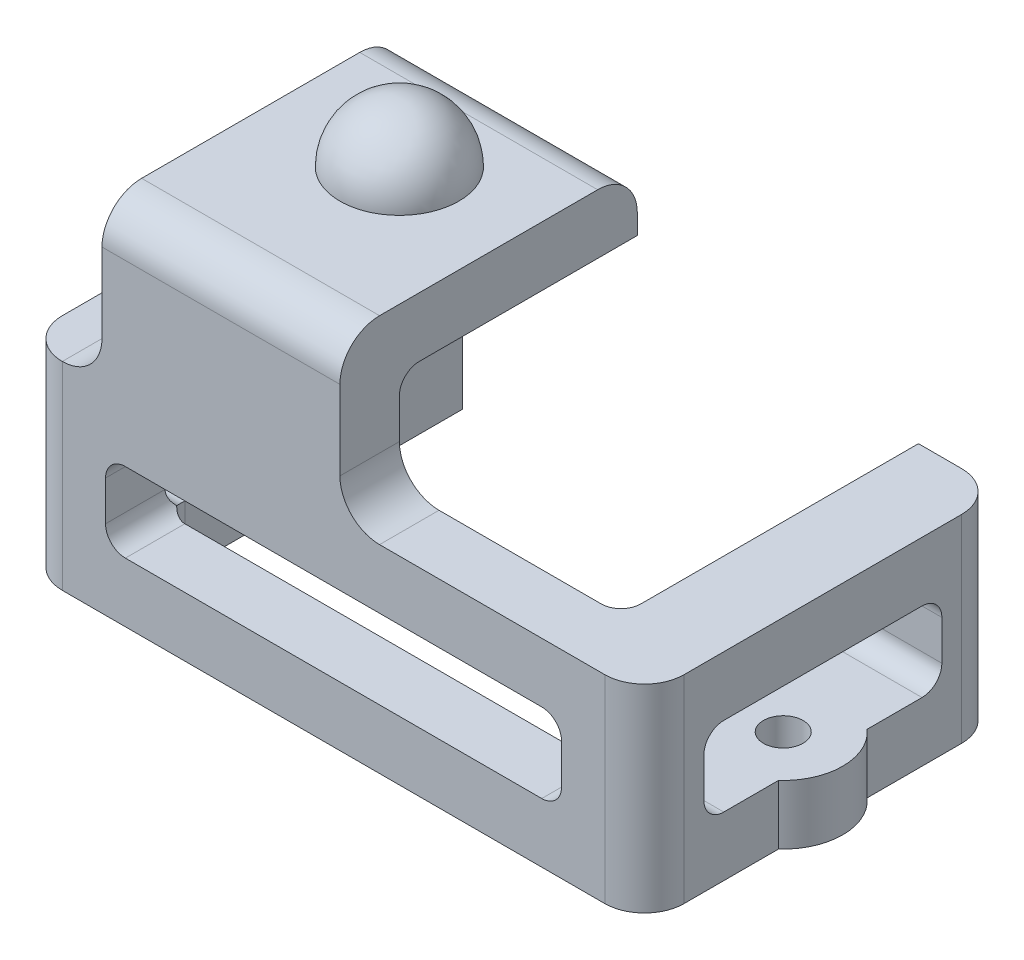
SolidWorks part; units mm, degrees
ref_plane "Plano frontal" through (0, 0, 0) normal (0, 0, 1) x (1, 0, 0)
ref_plane "Plano superior" through (0, 0, 0) normal (0, 1, 0) x (1, 0, 0)
ref_plane "Plano direito" through (0, 0, 0) normal (1, 0, 0) x (0, 0, -1)
sketch "Sketch1" plane through (0, 0, 0) normal (0, 1, 0) x (1, 0, 0)
  line L1 (-15.68, -9) -> (15.68, -9)
  line L2 (-15.68, -9) -> (-15.68, 9)
  line L3 (-15.68, 9) -> (15.68, 9)
  line L4 (15.68, -9) -> (15.68, 9)
  line L5 (-15.68, -9) -> (15.68, 9) construction
  line L6 (-15.68, 9) -> (15.68, -9) construction
  point P0 (0, 0)
  dimension "D1" = 31.36
  dimension "D2" = 18
extrude "Boss-Extrude1" add sketch "Sketch1" along normal mid plane 3
sketch "Sketch2" plane through (0, 1.5, 0) normal (0, 1, 0) x (1, 0, 0)
  line L0 (15.68, 9) -> (-15.68, 9) construction
  line L5 (-11.5, 9) -> (11.5, 9)
  line L6 (-11.5, 9) -> (-11.5, -6)
  line L7 (-11.5, -6) -> (11.5, -6)
  line L8 (11.5, 9) -> (11.5, -6)
  point P0 (0, 0)
  point P5 (0, 9)
  dimension "D1" = 23
  dimension "D2" = 6
extrude "Cut-Extrude1" cut sketch "Sketch2" against normal up to next
sketch "Sketch3" plane through (0, 1.5, 0) normal (0, 1, 0) x (1, 0, 0)
  line L1 (11.5, -6) -> (11.5, 9) construction
  line L2 (-11.5, 9) -> (-11.5, -6) construction
  circle A0 centre (13.68, 0) radius 1
  circle A1 centre (-13.68, 0) radius 1
  point P2 (0, 0)
  point P3 (25.9303, -1.6202)
  point P4 (0, 0)
  dimension "D3" = 2
  dimension "D4" = 2
  dimension "D1" = 2.18
  dimension "D2" = 2.18
extrude "Cut-Extrude2" cut sketch "Sketch3" against normal up to next
sketch "Sketch5" plane through (0, 1.5, 0) normal (0, 1, 0) x (1, 0, 0)
  line L0 (15.68, -9) -> (15.68, 9) construction
  line L1 (-11.5, 6) -> (-15.68, 6)
  line L2 (-11.5, 6) -> (-11.5, 9)
  line L3 (-11.5, 9) -> (-15.68, 9)
  line L4 (-15.68, 6) -> (-15.68, 9)
  line L5 (11.5, 6) -> (15.68, 6)
  line L6 (11.5, 6) -> (11.5, 9)
  line L7 (11.5, 9) -> (15.68, 9)
  line L8 (15.68, 6) -> (15.68, 9)
  line L9 (11.5, -9) -> (15.68, -9)
  line L10 (11.5, -9) -> (11.5, -6)
  line L11 (11.5, -6) -> (15.68, -6)
  line L12 (15.68, -9) -> (15.68, -6)
  line L14 (-15.68, -9) -> (-11.5, -9)
  line L15 (-15.68, -9) -> (-15.68, -6)
  line L16 (-15.68, -6) -> (-11.5, -6)
  line L17 (-11.5, -9) -> (-11.5, -6)
  line L20 (11.5, -6) -> (11.5, 9) construction
  line L21 (-11.5, 9) -> (-11.5, -6) construction
  point P24 (0, 0)
  point P26 (12.505, -6.4128)
  point P32 (15.5, -7.1503)
  dimension "D2" = 3
  dimension "D3" = 3
  dimension "D1" = 3
extrude "Boss-Extrude3" add sketch "Sketch5" along normal blind 4
sketch "Sketch6" plane through (0, 5.5, 0) normal (0, 1, 0) x (1, 0, 0)
  line L1 (-15.68, 9) -> (15.68, 9)
  line L2 (-15.68, 9) -> (-15.68, -9)
  line L3 (-15.68, -9) -> (15.68, -9)
  line L4 (15.68, 9) -> (15.68, -9)
extrude "Boss-Extrude4" add sketch "Sketch6" along normal blind 3
sketch "Sketch7" plane through (0, 5.5, 0) normal (0, -1, 0) x (1, 0, 0)
  line L1 (-11.5, 6) -> (11.5, 6)
  line L2 (-11.5, 6) -> (-11.5, -9)
  line L3 (-11.5, -9) -> (11.5, -9)
  line L4 (11.5, 6) -> (11.5, -9)
  line L6 (11.5, -9) -> (11.5, -6) construction
  line L7 (-11.5, -6) -> (-11.5, -9) construction
  line L8 (-11.5, 6) -> (-15.68, 6) construction
  line L9 (11.5, -9) -> (-11.5, -9) construction
  point P6 (0, 0)
  point P8 (0, 0)
  point P12 (0, 0)
extrude "Cut-Extrude3" cut sketch "Sketch7" against normal up to next
sketch "Sketch8" plane through (0, 0, 9) normal (0, 0, 1) x (1, 0, 0)
  line L0 (-15.68, 8.5) -> (15.68, 8.5) construction
  line L1 (-11.68, 8.5) -> (0.32, 8.5)
  line L2 (-11.68, 8.5) -> (-11.68, 13.5)
  line L3 (-11.68, 13.5) -> (0.32, 13.5)
  line L4 (0.32, 8.5) -> (0.32, 13.5)
  line L5 (-15.68, 8.5) -> (-15.68, -1.5) construction
  point P6 (-5.68, 13.5)
  dimension "D1" = 10
  dimension "D2" = 5
  dimension "D3" = 12
extrude "Boss-Extrude5" add sketch "Sketch8" against normal up to surface (3 mm away) up to face at (0, 7, 6)
sketch "Sketch9" plane through (0, 0, 6) normal (0, 0, -1) x (-1, 0, 0)
  line L0 (11.68, 8.5) -> (11.68, 13.5) construction
  line L1 (-0.32, 13.5) -> (11.68, 13.5)
  line L2 (-0.32, 13.5) -> (-0.32, 16.5)
  line L3 (-0.32, 16.5) -> (11.68, 16.5)
  line L4 (11.68, 13.5) -> (11.68, 16.5)
  dimension "D1" = 3
extrude "Boss-Extrude6" add sketch "Sketch9" along normal blind 12 and the other way up to surface (3 mm away) contours L4 L3 L2 L1 other way up to face at (-2.84, 7.25, 9)
sketch "Sketch10" plane through (0, 16.5, 0) normal (0, 1, 0) x (1, 0, 0)
  line L0 (-11.68, -9) -> (0.32, -9) construction
  line L1 (11.5, -6) -> (0.32, -6) construction
  line L2 (-8.68, 0) -> (-2.68, 0)
  circle A0 centre (-5.68, 0) radius 3
  point P4 (-5.68, -9)
  dimension "D2" = 6
  dimension "D1" = 6
revolve "Revolve1" add sketch "Sketch10" angle 180 about L2 region at (-5.68, 16.5, 1.2732) reverse direction yes
sketch "Sketch11" plane through (0, -1.5, 0) normal (0, -1, 0) x (1, 0, 0)
  line L0 (13.68, -3) -> (13.68, 3)
  line L1 (-13.68, 3) -> (-13.68, -3)
  circle A0 centre (13.68, 0) radius 3
  circle A1 centre (-13.68, 0) radius 3
  line M9 (15.68, -9) -> (15.68, 9)
  line M11 (-15.68, 9) -> (-15.68, -9)
  dimension "D1" = 6
  dimension "D2" = 6
extrude "Boss-Extrude7" add sketch "Sketch11" against normal up to surface (3 mm away) contours A1 M11 | A0 M9 region at (16.0863, -1.5, 0) region at (-16.0863, -1.5, 0) up to face at (-13.68, 1.5, 1)
fillet "Fillet1" radius 1 8 edges at (13.59, 5.5, 6) (13.59, 1.5, 6) (13.59, 1.5, -6) (-13.59, 1.5, -6) (-13.59, 1.5, 6) (-13.59, 5.5, 6) (13.59, 5.5, -6) (-13.59, 5.5, -6)
fillet "Fillet2" radius 1 4 edges at (-11.5, 1.5, 7.5) (-11.5, 5.5, 7.5) (11.5, 5.5, 7.5) (11.5, 1.5, 7.5)
fillet "Fillet3" radius 1 5 edges at (-5.68, 13.5, 6) (-11.5, 0.5, 6) (-11.5, 6.5, 6) (11.5, 6.5, 6) (11.5, 0.5, 6)
fillet "Fillet4" radius 2 4 edges at (-15.68, 3.5, -9) (-15.68, 3.5, 9) (15.68, 3.5, 9) (15.68, 3.5, -9)
fillet "Fillet5" radius 2 2 edges at (-5.68, 16.5, -6) (-5.68, 16.5, 9)
fillet "Fillet6" radius 2 2 edges at (-11.68, 8.5, 7.5) (0.32, 8.5, 7.5)
equation "\"D4@Sketch3\"=\"D3@Sketch3\""
equation "\"D2@Sketch3\"=\"D1@Sketch3\""
equation "\"D2@Sketch5\"=\"D1@Sketch5\""
equation "\"D3@Sketch5\"=\"D1@Sketch5\""
equation "\"D2@Sketch11\"=\"D1@Sketch11\""
